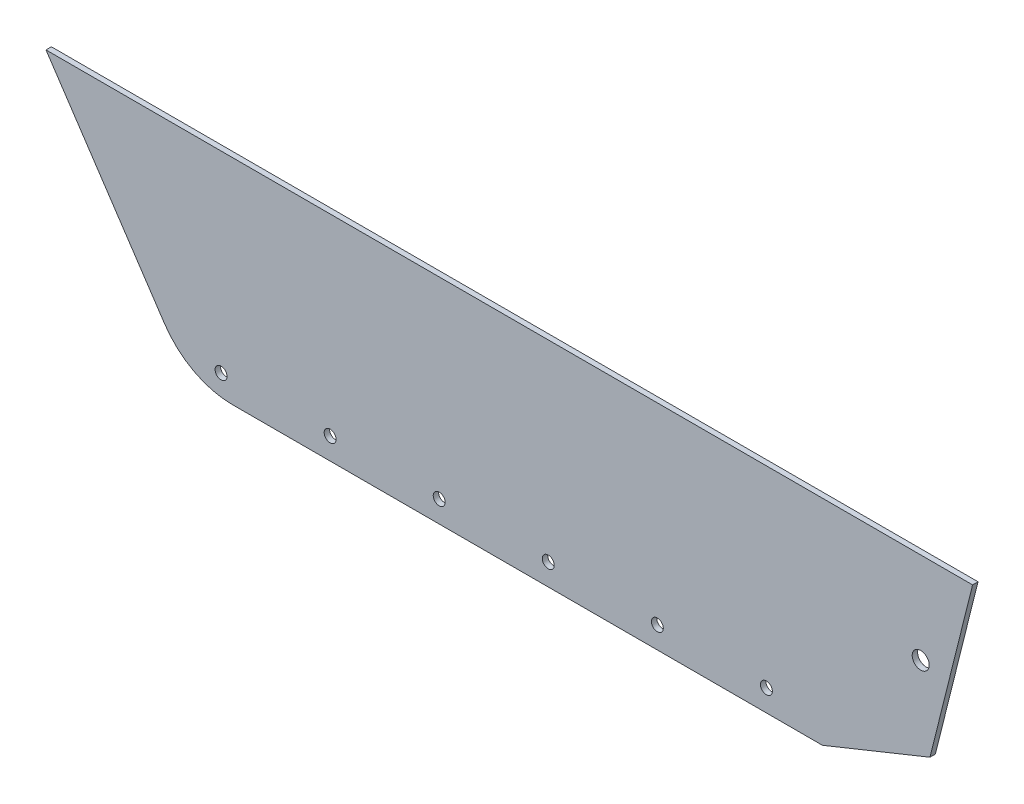
SolidWorks part; units mm, degrees
material "5052-H34"
ref_plane "Front Plane" through (0, 0, 0) normal (0, 0, 1) x (1, 0, 0)
ref_plane "Top Plane" through (0, 0, 0) normal (0, 1, 0) x (1, 0, 0)
ref_plane "Right Plane" through (0, 0, 0) normal (1, 0, 0) x (0, 0, -1)
sketch "Sketch1" plane through (0, 0, 0) normal (0, 0, 1) x (1, 0, 0)
  line L6 (-98.8794, 3.851) -> (-31.8794, -96.649)
  line L7 (428.1206, 28.9396) -> (403.1206, -71.149)
  line L9 (403.1206, -71.149) -> (366, -96.649)
  line L10 (-31.8794, -96.649) -> (366, -96.649)
  line L12 (-98.8794, 3.851) -> (-115.6052, 28.9396)
  line L13 (-115.6052, 28.9396) -> (428.1206, 28.9396)
  circle A0 centre (-12.8794, -83.899) radius 3.5
  circle A1 centre (51.1206, -83.899) radius 3.5
  circle A2 centre (115.1206, -83.899) radius 3.5
  circle A3 centre (179.1206, -83.899) radius 3.5
  circle A4 centre (243.1206, -83.899) radius 3.5
  circle A5 centre (307.1206, -83.899) radius 3.5
  point P0 (-48.8794, -71.149)
  point P2 (-31.8794, -96.649)
  point P8 (48, -83.899)
  point P9 (403.1206, -71.149)
  dimension "D2" = 64
  dimension "D4" = 64
  dimension "D15" = 7
  dimension "D1" = 25.5
  dimension "D3" = 75
  dimension "D5" = 25
  dimension "D6" = 96
  dimension "D7" = 527
  dimension "D8" = 180
  dimension "D9" = 64
  dimension "D10" = 64
  dimension "D11" = 64
  dimension "D12" = 123.69
  dimension "D13" = 12.75
  dimension "D14" = 543.7258
  dimension "D16" = 366
extrude "Boss-Extrude1" add sketch "Sketch1" along normal blind 3.175 contours L12 L13 L7 L9 L10 L6
extrude "Cut-Extrude1" cut sketch "Sketch1<4>" along normal through all contours A0 | A1 | A2 | A3 | A4 | A5 region at (-12.8794, -83.899, 0)
sketch "Sketch1<4>" plane through (0, 0, 0) normal (0, 0, 1) x (1, 0, 0) same geometry as "Sketch1"
sketch "Sketch2" plane through (0, 0, 0) normal (0, 0, -1) x (-1, 0, 0)
  circle A0 centre (-275.1206, -83.899) radius 6.5
  circle A2 centre (-233.5603, -132.5687) radius 6.5
  circle A3 centre (-192, -83.899) radius 6.5
  circle A4 centre (-128, -83.899) radius 6.5
  circle A5 centre (-64, -83.899) radius 6.5
  circle A6 centre (0, -83.899) radius 6.5
  dimension "D2" = 0
  dimension "D3" = 64
  dimension "D4" = 64
  dimension "D5" = 64
  dimension "D6" = 64
  dimension "D7" = 64
  dimension "D1" = 32
sketch "Sketch5" plane through (0, 0, 0) normal (0, 0, -1) x (-1, 0, 0)
  line L0 (48.8794, -71.149) -> (-14.2353, -96.649)
  line L1 (31.8794, -96.649) -> (-366, -96.649) construction
  line L2 (-14.2353, -96.649) -> (31.8794, -96.649)
  line L3 (31.8794, -96.649) -> (48.8794, -71.149)
  line L6 (-366, -96.649) -> (-403.1206, -71.149)
  line L7 (-403.1206, -71.149) -> (-352, -71.149)
  line L9 (-352, -71.149) -> (-326.5, -96.649)
  line L11 (-366, -96.649) -> (-326.5, -96.649)
  dimension "D1" = 22
  dimension "D2" = 45
extrude "Cut-Extrude2" [suppressed] cut sketch "Sketch5" against normal up to next
sketch "Sketch6" plane through (0, 0, 3.175) normal (0, 0, 1) x (1, 0, 0)
  line L0 (-48.8794, -71.149) -> (14.2353, -96.649)
  line L1 (-31.8794, -96.649) -> (366, -96.649) construction
  line L2 (14.2353, -96.649) -> (-31.8794, -96.649)
  line L3 (-31.8794, -96.649) -> (-48.8794, -71.149)
  dimension "D1" = 158
fillet "Fillet1" radius 48 1 edges at (-31.8794, -96.649, 1.5875)
sketch "Sketch7" plane through (0, 0, 3.175) normal (0, 0, 1) x (1, 0, 0)
  line L0 (403.1206, -71.149) -> (340.0059, -96.649)
  line L1 (-31.8794, -96.649) -> (366, -96.649) construction
  line L2 (340.0059, -96.649) -> (366, -96.649)
  line L3 (366, -96.649) -> (403.1206, -71.149)
  dimension "D1" = 22
extrude "Cut-Extrude3" cut sketch "Sketch7" against normal blind 10
sketch "Sketch9" plane through (0, 0, 0) normal (0, 0, -1) x (-1, 0, 0)
  line L0 (-403.1206, -71.149) -> (48.8794, -71.149)
  line L1 (48.8794, -71.149) -> (48.8794, -114.9143)
  line L2 (48.8794, -114.9143) -> (-403.1206, -114.9143)
  line L3 (-403.1206, -114.9143) -> (-403.1206, -71.149)
extrude "Cut-Extrude4" [suppressed] cut sketch "Sketch9" against normal blind 10
sketch "Sketch12" plane through (0, 0, 3.175) normal (0, 0, 1) x (1, 0, 0)
  circle A0 centre (397.6778, -24.6104) radius 5
extrude "Cut-Extrude5" cut sketch "Sketch12" against normal up to next
